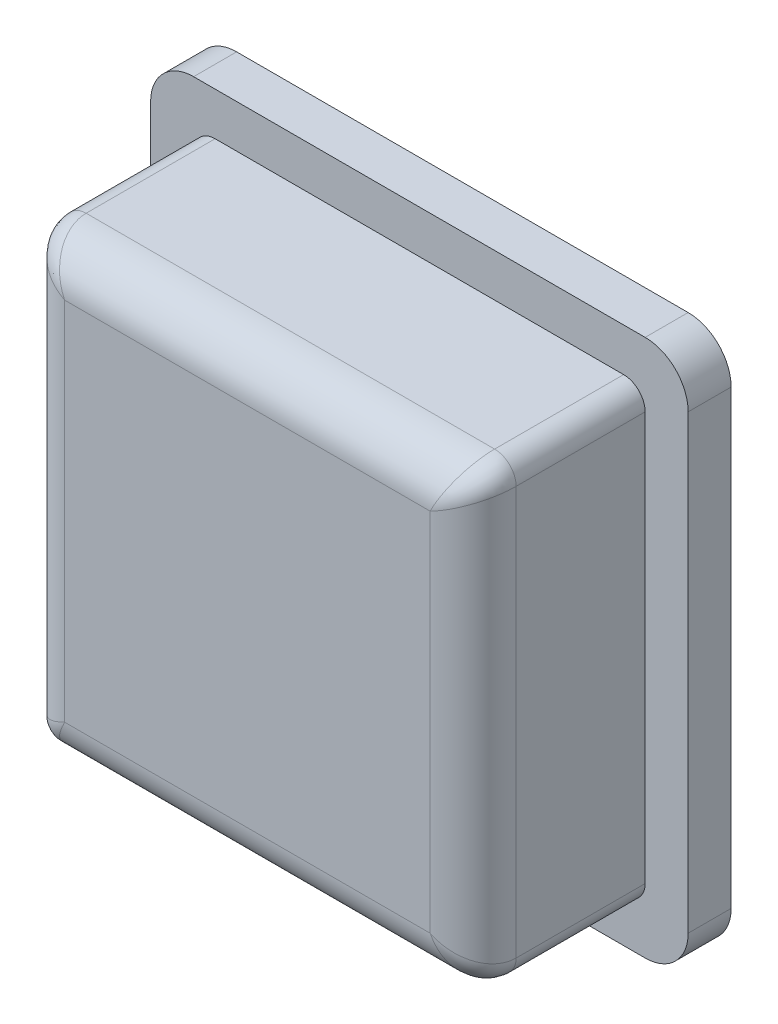
SolidWorks part; units mm, degrees
ref_plane "Front Plane" through (0, 0, 0) normal (0, 0, 1) x (1, 0, 0)
ref_plane "Top Plane" through (0, 0, 0) normal (0, 1, 0) x (1, 0, 0)
ref_plane "Right Plane" through (0, 0, 0) normal (1, 0, 0) x (0, 0, -1)
sketch "Sketch1" plane through (0, 0, 0) normal (0, 0, 1) x (1, 0, 0)
  line L0 (-5.25, 4.75) -> (-5.25, -4.75)
  line L1 (18.05, 3.05) -> (11.95, -3.05) construction
  line L2 (-18.05, 3.05) -> (-11.95, 3.05) construction
  line L3 (-18.05, 3.05) -> (-18.05, -3.05) construction
  line L4 (-18.05, -3.05) -> (-11.95, -3.05) construction
  line L5 (-11.95, 3.05) -> (-11.95, -3.05) construction
  line L6 (11.95, 3.05) -> (18.05, 3.05) construction
  line L7 (11.95, 3.05) -> (11.95, -3.05) construction
  line L8 (11.95, -3.05) -> (18.05, -3.05) construction
  line L9 (18.05, 3.05) -> (18.05, -3.05) construction
  line L10 (-3.05, 18.05) -> (3.05, 18.05) construction
  line L11 (-3.05, 18.05) -> (-3.05, 11.95) construction
  line L12 (-3.05, 11.95) -> (3.05, 11.95) construction
  line L13 (3.05, 18.05) -> (3.05, 11.95) construction
  line L14 (-3.05, -11.95) -> (3.05, -11.95) construction
  line L15 (-3.05, -11.95) -> (-3.05, -18.05) construction
  line L16 (-3.05, -18.05) -> (3.05, -18.05) construction
  line L17 (3.05, -11.95) -> (3.05, -18.05) construction
  line L18 (-4.75, -5.25) -> (4.75, -5.25)
  line L19 (5.25, -4.75) -> (5.25, 4.75)
  line L20 (4.75, 5.25) -> (-4.75, 5.25)
  line L24 (11.95, -3.05) -> (18.05, -3.05) construction
  line L25 (18.05, -3.05) -> (11.95, 3.05) construction
  line L26 (3.05, 18.05) -> (-3.05, 11.95) construction
  line L27 (3.05, 11.95) -> (-3.05, 18.05) construction
  line L28 (3.05, -11.95) -> (-3.05, -18.05) construction
  line L29 (3.05, -18.05) -> (-3.05, -11.95) construction
  line L30 (-15, 3.05) -> (-15, -3.05) construction
  line L31 (0.433, 19.25) -> (5.3405, 10.75) construction
  line L32 (4.9075, 10) -> (-4.9075, 10) construction
  line L33 (-5.3405, 10.75) -> (-0.433, 19.25) construction
  line L34 (19.25, -0.433) -> (10.75, -5.3405) construction
  line L35 (10.75, 5.3405) -> (19.25, 0.433) construction
  line L36 (10, -4.9075) -> (10, 4.9075) construction
  line L37 (-0.433, -19.25) -> (-5.3405, -10.75) construction
  line L38 (5.3405, -10.75) -> (0.433, -19.25) construction
  line L39 (-4.9075, -10) -> (4.9075, -10) construction
  line L40 (-19.25, 0.433) -> (-10.75, 5.3405) construction
  line L41 (-10.75, -5.3405) -> (-19.25, -0.433) construction
  line L42 (-10, 4.9075) -> (-10, -4.9075) construction
  line L44 (-5, 5.5) -> (5, 5.5) construction
  line L45 (-5.5, 5) -> (-5.5, -5) construction
  line L46 (-5, -5.5) -> (5, -5.5) construction
  line L47 (5.5, 5) -> (5.5, -5) construction
  circle A0 centre (0, 0) radius 20 construction
  circle A1 centre (-12.5, -10) radius 2 construction
  circle A2 centre (12.5, -10) radius 2 construction
  circle A3 centre (12.5, 10) radius 2 construction
  arc A4 (-4.9075, 10) -> (-5.3405, 10.75) centre (-4.9075, 10.5) cw construction
  arc A5 (5.3405, 10.75) -> (4.9075, 10) centre (4.9075, 10.5) cw construction
  arc A6 (0.433, 19.25) -> (-0.433, 19.25) centre (0, 19) ccw construction
  arc A7 (19.25, -0.433) -> (19.25, 0.433) centre (19, 0) ccw construction
  arc A8 (10, 4.9075) -> (10.75, 5.3405) centre (10.5, 4.9075) cw construction
  arc A9 (10.75, -5.3405) -> (10, -4.9075) centre (10.5, -4.9075) cw construction
  arc A10 (-0.433, -19.25) -> (0.433, -19.25) centre (0, -19) ccw construction
  arc A11 (4.9075, -10) -> (5.3405, -10.75) centre (4.9075, -10.5) cw construction
  arc A12 (-5.3405, -10.75) -> (-4.9075, -10) centre (-4.9075, -10.5) cw construction
  arc A13 (-19.25, 0.433) -> (-19.25, -0.433) centre (-19, 0) ccw construction
  arc A14 (-10, -4.9075) -> (-10.75, -5.3405) centre (-10.5, -4.9075) cw construction
  arc A15 (-10.75, 5.3405) -> (-10, 4.9075) centre (-10.5, 4.9075) cw construction
  arc A16 (-5, 5.5) -> (-5.5, 5) centre (-5, 5) ccw construction
  arc A17 (-5.5, -5) -> (-5, -5.5) centre (-5, -5) ccw construction
  arc A18 (5, -5.5) -> (5.5, -5) centre (5, -5) ccw construction
  arc A19 (5, 5.5) -> (5.5, 5) centre (5, 5) cw construction
  arc A20 (-5.25, -4.75) -> (-4.75, -5.25) centre (-4.75, -4.75) ccw
  arc A21 (4.75, -5.25) -> (5.25, -4.75) centre (4.75, -4.75) ccw
  arc A22 (5.25, 4.75) -> (4.75, 5.25) centre (4.75, 4.75) ccw
  arc A23 (-5.25, 4.75) -> (-4.75, 5.25) centre (-4.75, 4.75) cw
  point P33 (-15, 0)
  point P34 (0, 15)
  point P35 (0, -15)
  point P36 (15, 0)
  point P77 (0, 0)
  dimension "D1" = 40
  dimension "D5" = 4
  dimension "D14" = 0.5
  dimension "D17" = 0.5
  dimension "D12" = 0.5
  dimension "D2" = 0.25
  dimension "D3" = 25
  dimension "D4" = 12.5
  dimension "D6" = 0.25
  dimension "D7" = 6.1
  dimension "D8" = 0.25
  dimension "D9" = 11.95
  dimension "D10" = 11.95
  dimension "D11" = 0.25
  dimension "D13" = 3.05
  dimension "D16" = 10
  dimension "D18" = 10
  dimension "D15" = 4
extrude "Boss-Extrude1" add sketch "Sketch1" along normal blind 5
sketch "Sketch2" plane through (0, 0, 0) normal (0, 0, -1) x (-1, 0, 0)
  line L0 (4.75, -5.25) -> (-4.75, -5.25) construction
  line L1 (6.25, 6.25) -> (-6.25, 6.25)
  line L2 (6.25, 6.25) -> (6.25, -6.25)
  line L3 (6.25, -6.25) -> (-6.25, -6.25)
  line L4 (-6.25, 6.25) -> (-6.25, -6.25)
  line L5 (6.25, 6.25) -> (-6.25, -6.25) construction
  line L6 (6.25, -6.25) -> (-6.25, 6.25) construction
  line L7 (-5.25, -4.75) -> (-5.25, 4.75) construction
  point P0 (0, 0)
  dimension "D1" = 1
  dimension "D2" = 1
extrude "Boss-Extrude2" add sketch "Sketch2" against normal blind 1
fillet "Fillet1" radius 1 8 edges at (-5.1036, 5.1036, 5) (0, 5.25, 5) (5.1036, 5.1036, 5) (5.25, 0, 5) (5.1036, -5.1036, 5) (0, -5.25, 5) (-5.1036, -5.1036, 5) (-5.25, 0, 5)
fillet "Fillet2" radius 1 4 edges at (-6.25, -6.25, 0.5) (6.25, -6.25, 0.5) (6.25, 6.25, 0.5) (-6.25, 6.25, 0.5)
